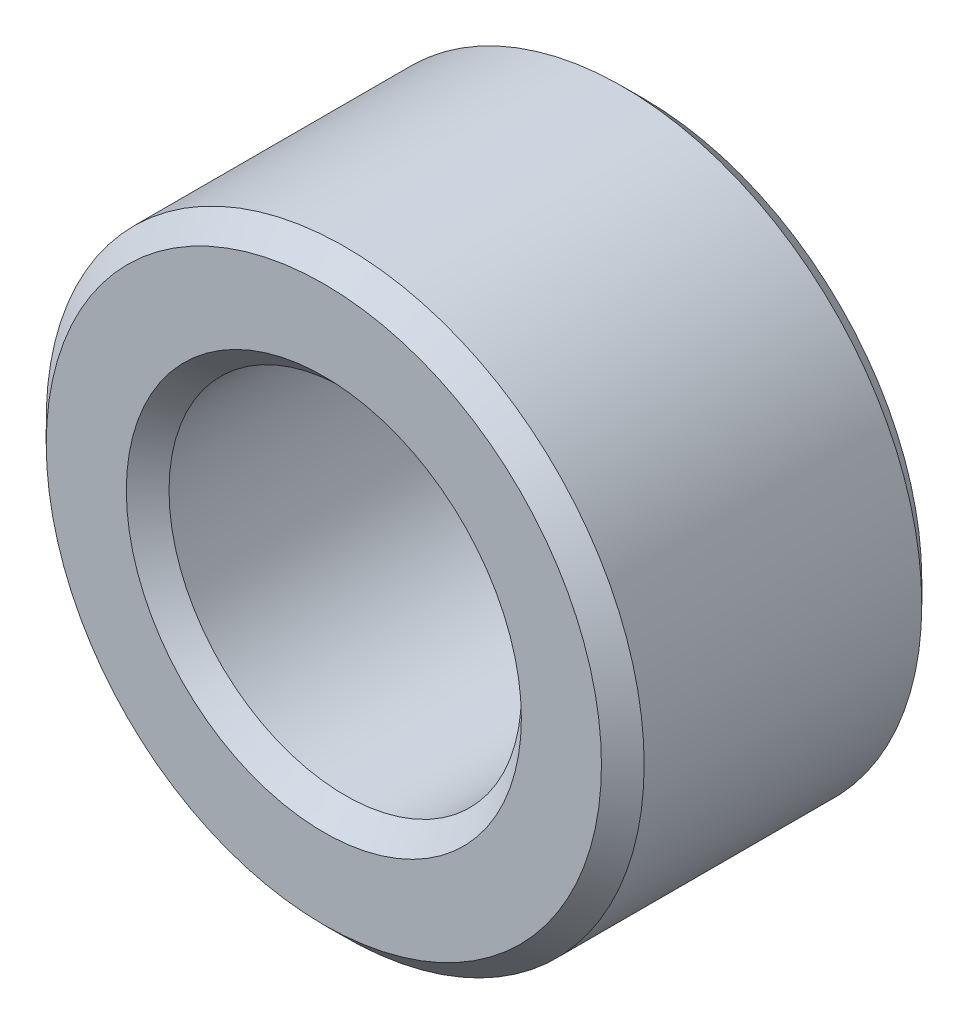
SolidWorks part; units mm, degrees
ref_plane "Front" through (0, 0, 0) normal (0, 0, 1) x (1, 0, 0)
ref_plane "Top" through (0, 0, 0) normal (0, 1, 0) x (1, 0, 0)
ref_plane "Right" through (0, 0, 0) normal (1, 0, 0) x (0, 0, -1)
sketch "Sketch1" plane through (0, 0, 0) normal (0, 0, 1) x (1, 0, 0)
  circle A0 centre (0, 0) radius 1.65
  circle A1 centre (0, 0) radius 2.8
  dimension "D1" = 3.3
  dimension "D2" = 5.6
extrude "Boss-Extrude1" add sketch "Sketch1" along normal blind 3
chamfer "Deburs" distance 0.2 angle 45 4 edges at (1.65, 0, 0) (1.65, 0, 3) (2.8, 0, 0) (2.8, 0, 3)
equation "\"D1@Sketch1\"=\"Hardware Clearance Hole Diameter@Box Assy.Assembly\"+.15mm"
equation "\"D2@Sketch1\"=\"Hardware Head Countersink Diameter@Box Assy.Assembly\"-.15mm"
